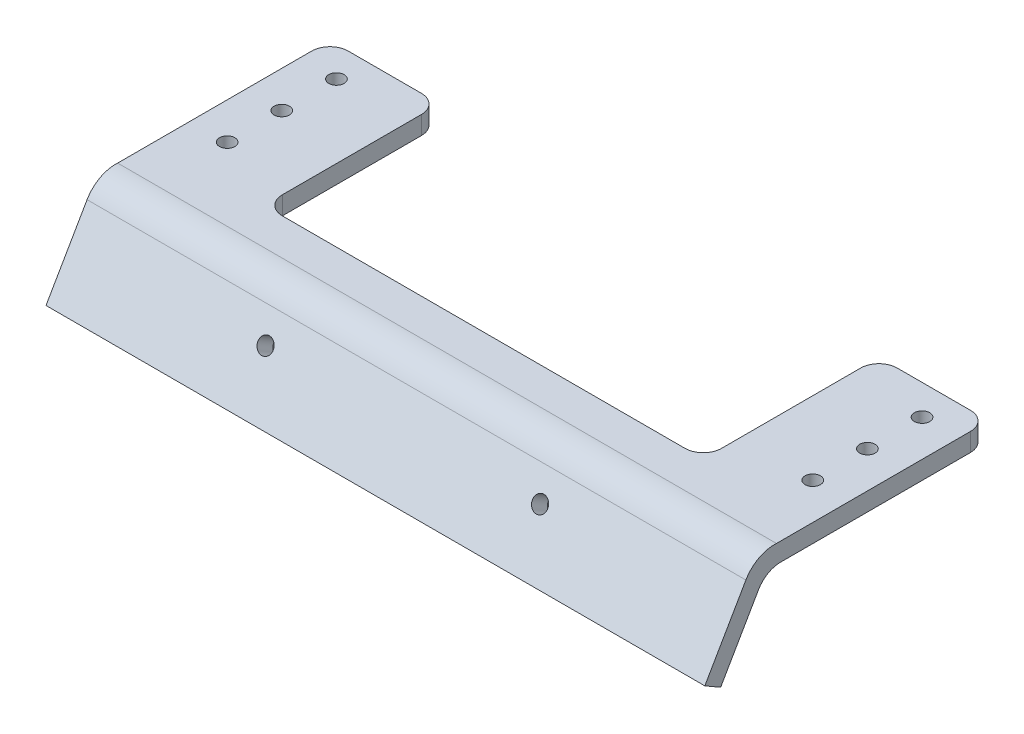
SolidWorks part; units mm, degrees
ref_plane "前视基准面" through (0, 0, 0) normal (0, 0, 1) x (1, 0, 0)
ref_plane "上视基准面" through (0, 0, 0) normal (0, 1, 0) x (1, 0, 0)
ref_plane "右视基准面" through (0, 0, 0) normal (1, 0, 0) x (0, 0, -1)
sketch "草图1" plane through (0, 0, 0) normal (0, 1, 0) x (1, 0, 0)
  line L0 (-104.5995, 0) -> (113.7141, 0) construction
  line L1 (-90, 31.5) -> (90, 31.5)
  line L2 (-90, 31.5) -> (-90, -31.5)
  line L3 (-90, -31.5) -> (90, -31.5)
  line L4 (90, 31.5) -> (90, -31.5)
  line L5 (-90, 31.5) -> (90, -31.5) construction
  line L6 (-90, -31.5) -> (90, 31.5) construction
  line L7 (0, 52.1269) -> (0, -44.2529) construction
  point P0 (0, 0)
  dimension "D1" = 180
  dimension "D2" = 63
extrude "凸台-拉伸1" add sketch "草图1" along normal blind 5
sketch "草图2" plane through (0, 5, 0) normal (0, 1, 0) x (1, 0, 0)
  line L0 (0, 43.6471) -> (0, -34.5822) construction
  line L1 (0, 23.27) -> (80, 23.27) construction
  line L2 (0, 8.34) -> (80, 8.34) construction
  line L3 (0, -6.59) -> (80, -6.59) construction
  line L4 (-90, -31.5) -> (90, -31.5) construction
  circle A0 centre (80, 23.27) radius 2.1
  circle A1 centre (80, 8.34) radius 2.1
  circle A2 centre (80, -6.59) radius 2.1
  circle A3 centre (-80, 23.27) radius 2.1
  circle A4 centre (-80, 8.34) radius 2.1
  circle A5 centre (-80, -6.59) radius 2.1
  dimension "D1" = 14.93
  dimension "D3" = 24.91
  dimension "D4" = 4.2
  dimension "D5" = 4.2
  dimension "D6" = 4.2
  dimension "D2" = 14.93
extrude "切除-拉伸1" cut sketch "草图2" against normal blind 5
sketch "草图3" plane through (-90, 0, 0) normal (-1, 0, 0) x (0, 0, 1)
  line L0 (26.5, 5) -> (29.3868, 0)
  line L1 (-31.5, 5) -> (31.5, 5) construction
  line L2 (26.5, 5) -> (31.5, 5)
  line L4 (-31.5, 0) -> (31.5, 0) construction
  line L5 (29.3868, 0) -> (31.5, 0)
  line L6 (31.5, 0) -> (31.5, 5)
  dimension "D1" = 5
  dimension "D2" = 120
extrude "切除-拉伸2" cut sketch "草图3" against normal blind 200
ref_plane "基准面4" through (0, 12.7248, 22.0401) normal (0, 0.5, 0.866) x (1, 0, 0)
sketch "草图5" plane through (0, 12.7248, 22.0401) normal (0, 0.5, 0.866) x (1, 0, 0)
  line L0 (90, -8.9199) -> (-90, -8.9199) construction
  line L1 (-90, -39.4199) -> (90, -39.4199)
  line L2 (-90, -39.4199) -> (-90, -8.9199)
  line L3 (-90, -8.9199) -> (90, -8.9199)
  line L4 (90, -39.4199) -> (90, -8.9199)
  line L5 (-90, -39.4199) -> (90, -8.9199) construction
  line L6 (-90, -8.9199) -> (90, -39.4199) construction
  line L7 (90, -8.9199) -> (90, -14.6934) construction
  point P0 (0, -24.1699)
  dimension "D1" = 30.5
extrude "凸台-拉伸2" add sketch "草图5" along normal blind 5
sketch "草图7" plane through (0, 15.2248, 26.3702) normal (0, 0.5, 0.866) x (1, 0, 0)
  line L0 (0, 12.4295) -> (0, -47.3047) construction
  line L1 (0, -24.4199) -> (37.5, -24.4199) construction
  line L3 (90, -8.9199) -> (-90, -8.9199) construction
  circle A0 centre (37.5, -24.4199) radius 2.1
  circle A1 centre (-37.5, -24.4199) radius 2.1
  dimension "D2" = 4.2
  dimension "D1" = 15.5
extrude "切除-拉伸3" cut sketch "草图7" against normal blind 5
fillet "圆角3" radius 9 1 edges at (0, 7.5, 30.8301)
fillet "圆角4" radius 7 1 edges at (0, 0, 29.3868)
sketch "草图8" plane through (0, 5, 0) normal (0, 1, 0) x (1, 0, 0)
  line L0 (0, 37.5106) -> (0, -25.0978) construction
  line L5 (90, -26.5) -> (-90, -26.5) construction
  line L6 (-60, 33.5) -> (60, 33.5)
  line L7 (-60, 33.5) -> (-60, -16.5)
  line L8 (-60, -16.5) -> (60, -16.5)
  line L9 (60, 33.5) -> (60, -16.5)
  line L10 (-60, 33.5) -> (60, -16.5) construction
  line L11 (-60, -16.5) -> (60, 33.5) construction
  point P0 (1.7654, 7.7684)
  point P1 (0, 8.5)
  dimension "D1" = 120
  dimension "D2" = 50
  dimension "D3" = 10
extrude "切除-拉伸4" cut sketch "草图8" against normal blind 5
fillet "圆角5" radius 5 6 edges at (-60, 2.5, 16.5) (60, 2.5, 16.5) (60, 2.5, -31.5) (90, 2.5, -31.5) (-90, 2.5, -31.5) (-60, 2.5, -31.5)
